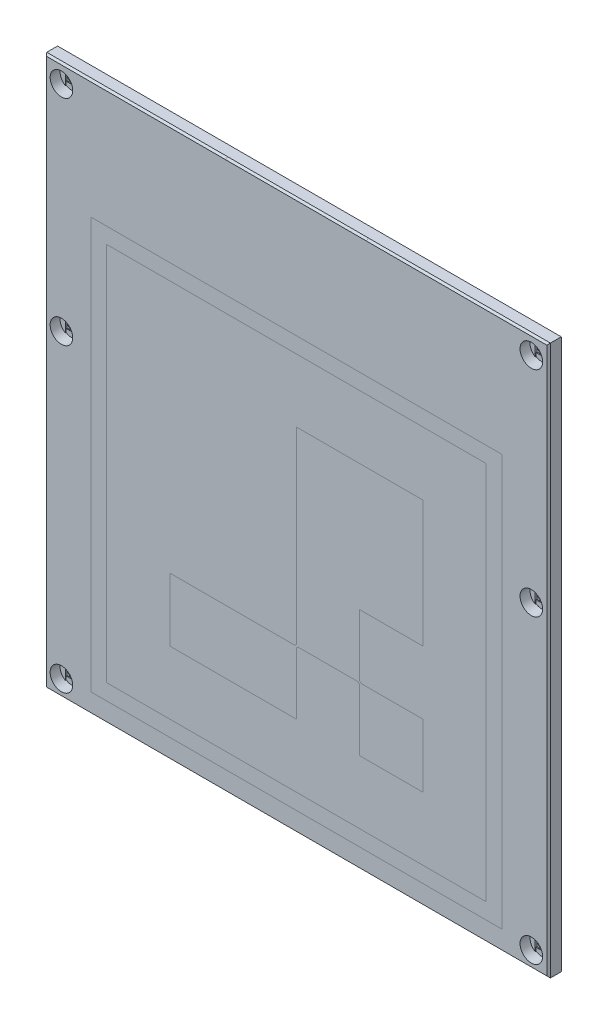
SolidWorks part; units mm, degrees
ref_plane "Front Plane" through (0, 0, 0) normal (0, 0, 1) x (1, 0, 0)
ref_plane "Top Plane" through (0, 0, 0) normal (0, 1, 0) x (1, 0, 0)
ref_plane "Right Plane" through (0, 0, 0) normal (1, 0, 0) x (0, 0, -1)
sketch "Sketch1" plane through (0, 0, 0) normal (0, 0, 1) x (1, 0, 0)
  line L0 (48, -68) -> (-48, -68) construction
  line L1 (56, -32.5) -> (56, -60) construction
  line L2 (56, 46) -> (56, -24.5) construction
  line L3 (-56, -24.5) -> (-56, 46) construction
  line L5 (-15, 54.4) -> (-15, 29) construction
  line L6 (-15, 29) -> (15, 29) construction
  line L7 (15, 29) -> (15, 54) construction
  line L8 (48, 54) -> (15, 54) construction
  line L9 (48, -68) -> (-48, -68) construction
  line L10 (56, -32.5) -> (56, -60) construction
  line L11 (56, 46) -> (56, -24.5) construction
  line L12 (-56, -24.5) -> (-56, 46) construction
  line L13 (-15, 54.4) -> (-48, 54.4) construction
  line L14 (-15, 54.4) -> (-15, 29) construction
  line L15 (-15, 29) -> (15, 29) construction
  line L16 (15, 29) -> (15, 54) construction
  line L17 (48, 54) -> (15, 54) construction
  line L18 (-15.25, 54.05) -> (-15.25, 28.75)
  line L19 (-55.65, 54.05) -> (-15.25, 54.05)
  line L20 (-55.65, 54.05) -> (-55.65, -67.65)
  line L21 (-55.65, -67.65) -> (55.825, -67.65)
  line L22 (55.825, 54.05) -> (55.825, -67.65)
  line L23 (-15.25, 28.75) -> (15.125, 28.75)
  line L24 (15.125, 28.75) -> (15.125, 54.05)
  line L25 (15.125, 54.05) -> (55.825, 54.05)
  circle A0 centre (-52, -64) radius 2.1 construction
  circle A3 centre (52, 50) radius 2.1 construction
  circle A4 centre (-52, 50) radius 2.1 construction
  circle A5 centre (-52, -64) radius 2.1 construction
  circle A6 centre (-52, 2.6) radius 2.15 construction
  circle A7 centre (52, 2.6) radius 2.15 construction
  circle A8 centre (52, 50) radius 2.1 construction
  circle A9 centre (-52, 50) radius 2.1 construction
  circle A10 centre (-52, 50) radius 1.35
  circle A11 centre (-52, 2.6) radius 1.35
  circle A12 centre (-52, -64) radius 1.35
  circle A13 centre (52, 50) radius 1.35
  circle A14 centre (52, 2.6) radius 1.35
  circle A15 centre (52, -64) radius 1.35
  circle A16 centre (-52, 2.6) radius 2.15 construction
  circle A17 centre (52, 2.6) radius 2.15 construction
  dimension "D5" = 2.7
  dimension "D1" = 0.35
  dimension "D2" = 0.35
  dimension "D3" = 0.35
  dimension "D4" = 0.35
  dimension "D6" = 0.25
  dimension "D7" = 0.25
  dimension "D8" = 0.25
extrude "Boss-Extrude1" add sketch "Sketch1" along normal blind 2.8
sketch "Sketch2" plane through (0, 0, 2.8) normal (0, 0, 1) x (1, 0, 0)
  line L5 (15.125, 28.75) -> (-15.25, 28.75) construction
  line L8 (-45.5, -63.25) -> (45.5, -63.25)
  line L9 (-45.5, -63.25) -> (-45.5, 27.75)
  line L10 (-45.5, 27.75) -> (45.5, 27.75)
  line L11 (45.5, -63.25) -> (45.5, 27.75)
  line L31 (-42, 24.25) -> (-28, 24.25)
  line L32 (-42, 24.25) -> (-42, 10.25)
  line L33 (-42, 10.25) -> (-28, 10.25)
  line L34 (-28, 24.25) -> (-28, 10.25)
  line L35 (-28, 24.25) -> (-14, 24.25)
  line L36 (-28, 24.25) -> (-28, 10.25)
  line L37 (-28, 10.25) -> (-14, 10.25)
  line L38 (-14, 24.25) -> (-14, 10.25)
  line L39 (-14, 24.25) -> (0, 24.25)
  line L40 (-14, 24.25) -> (-14, 10.25)
  line L41 (-14, 10.25) -> (0, 10.25)
  line L42 (0, 24.25) -> (0, 10.25)
  line L43 (0, 24.25) -> (14, 24.25)
  line L44 (0, 24.25) -> (0, 10.25)
  line L45 (0, 10.25) -> (14, 10.25)
  line L46 (14, 24.25) -> (14, 10.25)
  line L47 (14, 24.25) -> (28, 24.25)
  line L48 (14, 24.25) -> (14, 10.25)
  line L49 (14, 10.25) -> (28, 10.25)
  line L50 (28, 24.25) -> (28, 10.25)
  line L51 (28, 24.25) -> (42, 24.25)
  line L52 (28, 24.25) -> (28, 10.25)
  line L53 (28, 10.25) -> (42, 10.25)
  line L54 (42, 24.25) -> (42, 10.25)
  line L55 (-42, 10.25) -> (-28, 10.25)
  line L56 (-42, 10.25) -> (-42, -3.75)
  line L57 (-42, -3.75) -> (-28, -3.75)
  line L58 (-28, 10.25) -> (-28, -3.75)
  line L59 (-28, -3.75) -> (-14, -3.75)
  line L60 (-28, -3.75) -> (-28, 10.25)
  line L61 (-28, 10.25) -> (-14, 10.25)
  line L62 (-14, -3.75) -> (-14, 10.25)
  line L63 (-14, -3.75) -> (0, -3.75)
  line L64 (-14, -3.75) -> (-14, 10.25)
  line L65 (-14, 10.25) -> (0, 10.25)
  line L66 (0, -3.75) -> (0, 10.25)
  line L67 (0, -3.75) -> (14, -3.75)
  line L68 (0, -3.75) -> (0, 10.25)
  line L69 (0, 10.25) -> (14, 10.25)
  line L70 (14, -3.75) -> (14, 10.25)
  line L71 (14, -3.75) -> (28, -3.75)
  line L72 (14, -3.75) -> (14, 10.25)
  line L73 (14, 10.25) -> (28, 10.25)
  line L74 (28, -3.75) -> (28, 10.25)
  line L75 (28, -3.75) -> (42, -3.75)
  line L76 (28, -3.75) -> (28, 10.25)
  line L77 (28, 10.25) -> (42, 10.25)
  line L78 (42, -3.75) -> (42, 10.25)
  line L79 (42, -3.75) -> (28, -3.75)
  line L80 (42, -3.75) -> (42, -17.75)
  line L81 (42, -17.75) -> (28, -17.75)
  line L82 (28, -3.75) -> (28, -17.75)
  line L83 (14, -3.75) -> (28, -3.75)
  line L84 (14, -3.75) -> (14, -17.75)
  line L85 (14, -17.75) -> (28, -17.75)
  line L86 (28, -3.75) -> (28, -17.75)
  line L87 (0, -3.75) -> (14, -3.75)
  line L88 (0, -3.75) -> (0, -17.75)
  line L89 (0, -17.75) -> (14, -17.75)
  line L90 (14, -3.75) -> (14, -17.75)
  line L91 (-14, -3.75) -> (0, -3.75)
  line L92 (-14, -3.75) -> (-14, -17.75)
  line L93 (-14, -17.75) -> (0, -17.75)
  line L94 (0, -3.75) -> (0, -17.75)
  line L95 (-28, -3.75) -> (-14, -3.75)
  line L96 (-28, -3.75) -> (-28, -17.75)
  line L97 (-28, -17.75) -> (-14, -17.75)
  line L98 (-14, -3.75) -> (-14, -17.75)
  line L99 (-42, -3.75) -> (-28, -3.75)
  line L100 (-42, -3.75) -> (-42, -17.75)
  line L101 (-42, -17.75) -> (-28, -17.75)
  line L102 (-28, -3.75) -> (-28, -17.75)
  line L103 (-42, -17.75) -> (-28, -17.75)
  line L104 (-42, -17.75) -> (-42, -31.75)
  line L105 (-42, -31.75) -> (-28, -31.75)
  line L106 (-28, -17.75) -> (-28, -31.75)
  line L107 (-28, -31.75) -> (-14, -31.75)
  line L108 (-28, -31.75) -> (-28, -17.75)
  line L109 (-28, -17.75) -> (-14, -17.75)
  line L110 (-14, -31.75) -> (-14, -17.75)
  line L111 (-14, -17.75) -> (0, -17.75)
  line L112 (-14, -17.75) -> (-14, -31.75)
  line L113 (-14, -31.75) -> (0, -31.75)
  line L114 (0, -17.75) -> (0, -31.75)
  line L115 (0, -31.75) -> (14, -31.75)
  line L116 (0, -31.75) -> (0, -17.75)
  line L117 (0, -17.75) -> (14, -17.75)
  line L118 (14, -31.75) -> (14, -17.75)
  line L119 (14, -31.75) -> (28, -31.75)
  line L120 (14, -31.75) -> (14, -17.75)
  line L121 (14, -17.75) -> (28, -17.75)
  line L122 (28, -31.75) -> (28, -17.75)
  line L123 (28, -31.75) -> (42, -31.75)
  line L124 (28, -31.75) -> (28, -17.75)
  line L125 (28, -17.75) -> (42, -17.75)
  line L126 (42, -31.75) -> (42, -17.75)
  line L127 (-42, -31.75) -> (-28, -31.75)
  line L128 (-42, -31.75) -> (-42, -45.75)
  line L129 (-42, -45.75) -> (-28, -45.75)
  line L130 (-28, -31.75) -> (-28, -45.75)
  line L131 (-28, -45.75) -> (-14, -45.75)
  line L132 (-28, -45.75) -> (-28, -31.75)
  line L133 (-28, -31.75) -> (-14, -31.75)
  line L134 (-14, -45.75) -> (-14, -31.75)
  line L135 (-14, -45.75) -> (0, -45.75)
  line L136 (-14, -45.75) -> (-14, -31.75)
  line L137 (-14, -31.75) -> (0, -31.75)
  line L138 (0, -45.75) -> (0, -31.75)
  line L139 (0, -45.75) -> (14, -45.75)
  line L140 (0, -45.75) -> (0, -31.75)
  line L141 (0, -31.75) -> (14, -31.75)
  line L142 (14, -45.75) -> (14, -31.75)
  line L143 (14, -45.75) -> (28, -45.75)
  line L144 (14, -45.75) -> (14, -31.75)
  line L145 (14, -31.75) -> (28, -31.75)
  line L146 (28, -45.75) -> (28, -31.75)
  line L147 (28, -45.75) -> (42, -45.75)
  line L148 (28, -45.75) -> (28, -31.75)
  line L149 (28, -31.75) -> (42, -31.75)
  line L150 (42, -45.75) -> (42, -31.75)
  line L151 (42, -45.75) -> (28, -45.75)
  line L152 (42, -45.75) -> (42, -59.75)
  line L153 (42, -59.75) -> (28, -59.75)
  line L154 (28, -45.75) -> (28, -59.75)
  line L155 (28, -59.75) -> (14, -59.75)
  line L156 (28, -59.75) -> (28, -45.75)
  line L157 (28, -45.75) -> (14, -45.75)
  line L158 (14, -59.75) -> (14, -45.75)
  line L159 (0, -45.75) -> (14, -45.75)
  line L160 (0, -45.75) -> (0, -59.75)
  line L161 (0, -59.75) -> (14, -59.75)
  line L162 (14, -45.75) -> (14, -59.75)
  line L163 (-14, -45.75) -> (0, -45.75)
  line L164 (-14, -45.75) -> (-14, -59.75)
  line L165 (-14, -59.75) -> (0, -59.75)
  line L166 (0, -45.75) -> (0, -59.75)
  line L167 (-28, -45.75) -> (-14, -45.75)
  line L168 (-28, -45.75) -> (-28, -59.75)
  line L169 (-28, -59.75) -> (-14, -59.75)
  line L170 (-14, -45.75) -> (-14, -59.75)
  line L171 (-42, -45.75) -> (-28, -45.75)
  line L172 (-42, -45.75) -> (-42, -59.75)
  line L173 (-42, -59.75) -> (-28, -59.75)
  line L174 (-28, -45.75) -> (-28, -59.75)
  point P3 (0, 27.75)
  point P58 (-45.5, -17.75)
  dimension "D1" = 1
  dimension "D2" = 91
  dimension "D3" = 14
sketch "Sketch3" plane through (0, 0, 2.8) normal (0, 0, 1) x (1, 0, 0)
  circle A0 centre (-52, 50) radius 2.5
  circle A1 centre (-52, 2.6) radius 2.5
  circle A2 centre (-52, -64) radius 2.5
  circle A3 centre (52, -64) radius 2.5
  circle A4 centre (52, 2.6) radius 2.5
  circle A5 centre (52, 50) radius 2.5
  dimension "D1" = 5
extrude "Cut-Extrude1" cut sketch "Sketch3" against normal blind 2.2
sketch "Sketch4" plane through (0, 0, 0) normal (0, 0, -1) x (-1, 0, 0)
  line L0 (-15.125, 28.75) -> (15.25, 28.75) construction
  line L1 (-45.65, -57.65) -> (45.65, -57.65)
  line L2 (-45.65, -57.65) -> (-45.65, 27.75)
  line L3 (-45.65, 27.75) -> (45.65, 27.75)
  line L4 (45.65, -57.65) -> (45.65, 27.75)
  line L5 (-45.65, -57.65) -> (45.65, 27.75) construction
  line L6 (-45.65, 27.75) -> (45.65, -57.65) construction
  line L7 (55.65, 54.05) -> (55.65, -67.65) construction
  line L8 (55.65, -67.65) -> (-55.825, -67.65) construction
  point P0 (0, -14.95)
  point P9 (0, 27.75)
  dimension "D1" = 1
  dimension "D2" = 10
  dimension "D3" = 10
extrude "Cut-Extrude2" cut sketch "Sketch4" against normal blind 1.5
sketch "Sketch5" plane through (0, 0, 0.6) normal (0, 0, 1) x (1, 0, 0)
  line L2 (-53.35, 47.8958) -> (-53.35, 52.1042)
  line L4 (-50.65, 47.8958) -> (-50.65, 52.1042)
  line L5 (-53.35, 47.8958) -> (-50.65, 52.1042) construction
  line L6 (-53.35, 52.1042) -> (-50.65, 47.8958) construction
  line L8 (-53.35, 0.4958) -> (-53.35, 4.7042)
  line L10 (-50.65, 0.4958) -> (-50.65, 4.7042)
  line L11 (-53.35, 0.4958) -> (-50.65, 4.7042) construction
  line L12 (-53.35, 4.7042) -> (-50.65, 0.4958) construction
  line L14 (-53.35, -66.1042) -> (-53.35, -61.8958)
  line L16 (-50.65, -66.1042) -> (-50.65, -61.8958)
  line L17 (-53.35, -66.1042) -> (-50.65, -61.8958) construction
  line L18 (-53.35, -61.8958) -> (-50.65, -66.1042) construction
  circle A0 centre (-52, 50) radius 2.5 construction
  circle A1 centre (-52, 50) radius 1.35 construction
  arc A2 (-50.65, 52.1042) -> (-53.35, 52.1042) centre (-52, 50) ccw
  arc A3 (-53.35, 47.8958) -> (-50.65, 47.8958) centre (-52, 50) ccw
  circle A4 centre (-52, 2.6) radius 2.5 construction
  circle A5 centre (-52, 2.6) radius 1.35 construction
  circle A6 centre (-52, 2.6) radius 2.5 construction
  arc A7 (-50.65, 4.7042) -> (-53.35, 4.7042) centre (-52, 2.6) ccw
  arc A8 (-53.35, 0.4958) -> (-50.65, 0.4958) centre (-52, 2.6) ccw
  circle A9 centre (-52, -64) radius 2.5 construction
  circle A10 centre (-52, -64) radius 1.35 construction
  circle A11 centre (-52, -64) radius 2.5 construction
  arc A12 (-50.65, -61.8958) -> (-53.35, -61.8958) centre (-52, -64) ccw
  arc A13 (-53.35, -66.1042) -> (-50.65, -66.1042) centre (-52, -64) ccw
  point P0 (-52, 50)
  point P10 (-52, 2.6)
  point P22 (-52, -64)
extrude "Cut-Extrude3" cut sketch "Sketch5" against normal blind 0.2
sketch "Sketch6" plane through (0, 0, 0.4) normal (0, 0, 1) x (1, 0, 0)
  line L0 (-50.65, -66.1042) -> (-50.65, -61.8958) construction
  line L1 (-53.35, -65.35) -> (-50.65, -65.35)
  line L2 (-53.35, -65.35) -> (-53.35, -62.65)
  line L3 (-53.35, -62.65) -> (-50.65, -62.65)
  line L4 (-50.65, -65.35) -> (-50.65, -62.65)
  line L5 (-53.35, -65.35) -> (-50.65, -62.65) construction
  line L6 (-53.35, -62.65) -> (-50.65, -65.35) construction
  line L7 (-50.65, 0.4958) -> (-50.65, 4.7042) construction
  line L8 (-53.35, 1.25) -> (-50.65, 1.25)
  line L9 (-53.35, 1.25) -> (-53.35, 3.95)
  line L10 (-53.35, 3.95) -> (-50.65, 3.95)
  line L11 (-50.65, 1.25) -> (-50.65, 3.95)
  line L12 (-53.35, 1.25) -> (-50.65, 3.95) construction
  line L13 (-53.35, 3.95) -> (-50.65, 1.25) construction
  line L14 (-50.65, 47.8958) -> (-50.65, 52.1042) construction
  line L15 (-53.35, 48.65) -> (-50.65, 48.65)
  line L16 (-53.35, 48.65) -> (-53.35, 51.35)
  line L17 (-53.35, 51.35) -> (-50.65, 51.35)
  line L18 (-50.65, 48.65) -> (-50.65, 51.35)
  line L19 (-53.35, 48.65) -> (-50.65, 51.35) construction
  line L20 (-53.35, 51.35) -> (-50.65, 48.65) construction
  arc A0 (-50.65, -64) -> (-53.35, -64) centre (-52, -64) ccw construction
  arc A1 (-50.65, 2.6) -> (-53.35, 2.6) centre (-52, 2.6) ccw construction
  arc A2 (-50.65, 50) -> (-53.35, 50) centre (-52, 50) ccw construction
  point P0 (-52, -64)
  point P11 (-52, 2.6)
  point P22 (-52, 50)
extrude "Cut-Extrude4" cut sketch "Sketch6" against normal blind 0.2
mirror "Mirror1" about plane through (0, 0, 0) normal (1, 0, 0) of "Cut-Extrude4", "Cut-Extrude3"
chamfer "Chamfer1" distance 0.4 angle 45 8 edges at (0.0875, -67.65, 2.8) (55.825, -6.8, 2.8) (35.475, 54.05, 2.8) (15.125, 41.4, 2.8) (-0.0625, 28.75, 2.8) (-15.25, 41.4, 2.8) (-35.45, 54.05, 2.8) (-55.65, -6.8, 2.8)
sketch "Sketch7" plane through (0, 0, 2.8) normal (0, 0, 1) x (1, 0, 0)
  line L0 (28, 24.25) -> (42, 24.25) construction
  line L1 (14, 24.25) -> (28, 24.25) construction
  line L2 (0, 24.25) -> (14, 24.25) construction
  line L3 (-14, 24.25) -> (0, 24.25) construction
  line L4 (-28, 24.25) -> (-14, 24.25) construction
  line L5 (-42, 24.25) -> (-28, 24.25) construction
  line L6 (-42, 24.25) -> (-42, 10.25) construction
  line L7 (-42, 10.25) -> (-42, -3.75) construction
  line L8 (-42, -3.75) -> (-42, -17.75) construction
  line L9 (-42, -17.75) -> (-42, -31.75) construction
  line L10 (-42, -31.75) -> (-42, -45.75) construction
  line L11 (-42, -45.75) -> (-42, -59.75) construction
  line L12 (-42, -59.75) -> (-28, -59.75) construction
  line L13 (-28, -59.75) -> (-14, -59.75) construction
  line L14 (-14, -59.75) -> (0, -59.75) construction
  line L15 (0, -59.75) -> (14, -59.75) construction
  line L16 (28, -59.75) -> (14, -59.75) construction
  line L17 (42, -59.75) -> (28, -59.75) construction
  line L18 (42, -45.75) -> (42, -59.75) construction
  line L19 (42, -45.75) -> (42, -31.75) construction
  line L20 (42, -31.75) -> (42, -17.75) construction
  line L21 (42, -3.75) -> (42, -17.75) construction
  line L22 (42, -3.75) -> (42, 10.25) construction
  line L23 (42, 24.25) -> (42, 10.25) construction
  line L24 (45.5, -63.25) -> (45.5, 27.75) construction
  line L25 (-45.5, -63.25) -> (45.5, -63.25) construction
  line L26 (-45.5, -63.25) -> (-45.5, 27.75) construction
  line L27 (-45.5, 27.75) -> (45.5, 27.75) construction
  line L28 (28, 24.25) -> (42, 24.25)
  line L29 (14, 24.25) -> (28, 24.25)
  line L30 (0, 24.25) -> (14, 24.25)
  line L31 (-14, 24.25) -> (0, 24.25)
  line L32 (-28, 24.25) -> (-14, 24.25)
  line L33 (-42, 24.25) -> (-28, 24.25)
  line L34 (-42, 24.25) -> (-42, 10.25)
  line L35 (-42, 10.25) -> (-42, -3.75)
  line L36 (-42, -3.75) -> (-42, -17.75)
  line L37 (-42, -17.75) -> (-42, -31.75)
  line L38 (-42, -31.75) -> (-42, -45.75)
  line L39 (-42, -45.75) -> (-42, -59.75)
  line L40 (-42, -59.75) -> (-28, -59.75)
  line L41 (-28, -59.75) -> (-14, -59.75)
  line L42 (-14, -59.75) -> (0, -59.75)
  line L43 (0, -59.75) -> (14, -59.75)
  line L44 (28, -59.75) -> (14, -59.75)
  line L45 (42, -59.75) -> (28, -59.75)
  line L46 (42, -45.75) -> (42, -59.75)
  line L47 (42, -45.75) -> (42, -31.75)
  line L48 (42, -31.75) -> (42, -17.75)
  line L49 (42, -3.75) -> (42, -17.75)
  line L50 (42, -3.75) -> (42, 10.25)
  line L51 (42, 24.25) -> (42, 10.25)
  line L52 (45.5, -63.25) -> (45.5, 27.75)
  line L53 (-45.5, -63.25) -> (45.5, -63.25)
  line L54 (-45.5, -63.25) -> (-45.5, 27.75)
  line L55 (-45.5, 27.75) -> (45.5, 27.75)
extrude "Cut-Extrude5" cut sketch "Sketch7" against normal blind 0.4
sketch "Sketch8" plane through (0, 0, 2.4) normal (0, 0, 1) x (1, 0, 0)
  line L0 (-42, -59.75) -> (42, -59.75) construction
  line L1 (42, -59.75) -> (42, 24.25) construction
  line L2 (42, 24.25) -> (-42, 24.25) construction
  line L3 (-42, 24.25) -> (-42, -59.75) construction
  line L4 (-45.5, -63.25) -> (45.5, -63.25)
  line L5 (45.5, -63.25) -> (45.5, 27.75)
  line L6 (45.5, 27.75) -> (-45.5, 27.75)
  line L7 (-45.5, 27.75) -> (-45.5, -63.25)
  line L8 (-45.5, -63.25) -> (45.5, -63.25)
  line L9 (45.5, -63.25) -> (45.5, 27.75)
  line L10 (45.5, 27.75) -> (-45.5, 27.75)
  line L11 (-45.5, 27.75) -> (-45.5, -63.25)
  line L12 (-42, -59.75) -> (42, -59.75)
  line L13 (42, -59.75) -> (42, 24.25)
  line L14 (42, 24.25) -> (-42, 24.25)
  line L15 (-42, 24.25) -> (-42, -59.75)
  dimension "D1" = 0
extrude "Boss-Extrude2" add sketch "Sketch8" along normal up to surface (0.4 mm away) separate body up to face at (0, -17.75, 2.8)
sketch "Sketch9" plane through (0, 0, 2.8) normal (0, 0, 1) x (1, 0, 0)
  line L40 (-28, -31.75) -> (-28, -45.75) construction
  line L41 (-28, -31.75) -> (-14, -31.75) construction
  line L42 (-14, -31.75) -> (0, -31.75) construction
  line L43 (0, -17.75) -> (0, -31.75) construction
  line L44 (0, -3.75) -> (0, -17.75) construction
  line L45 (0, -3.75) -> (0, 10.25) construction
  line L46 (0, 10.25) -> (14, 10.25) construction
  line L47 (14, 10.25) -> (28, 10.25) construction
  line L48 (28, -3.75) -> (28, 10.25) construction
  line L49 (28, -3.75) -> (28, -17.75) construction
  line L50 (14, -17.75) -> (28, -17.75) construction
  line L51 (14, -31.75) -> (14, -17.75) construction
  line L52 (14, -31.75) -> (28, -31.75) construction
  line L53 (28, -45.75) -> (28, -31.75) construction
  line L54 (14, -45.75) -> (28, -45.75) construction
  line L55 (14, -45.75) -> (14, -31.75) construction
  line L56 (0, -31.75) -> (14, -31.75) construction
  line L57 (0, -45.75) -> (0, -31.75) construction
  line L58 (-14, -45.75) -> (0, -45.75) construction
  line L59 (-28, -45.75) -> (-14, -45.75) construction
  line L60 (-28, -31.75) -> (-28, -45.75)
  line L61 (-28, -31.75) -> (-14, -31.75)
  line L62 (-14, -31.75) -> (-0.3536, -31.75)
  line L63 (0, -17.75) -> (0, -31.3964)
  line L64 (0, -3.75) -> (0, -17.75)
  line L65 (0, -3.75) -> (0, 10.25)
  line L66 (0, 10.25) -> (14, 10.25)
  line L67 (14, 10.25) -> (28, 10.25)
  line L68 (28, -3.75) -> (28, 10.25)
  line L69 (28, -3.75) -> (28, -17.75)
  line L70 (14, -17.75) -> (28, -17.75)
  line L71 (14, -31.3964) -> (14, -17.75)
  line L72 (14.3536, -31.75) -> (28, -31.75)
  line L73 (28, -45.75) -> (28, -31.75)
  line L74 (14, -45.75) -> (28, -45.75)
  line L75 (14, -45.75) -> (14, -32.1036)
  line L76 (0.3536, -31.75) -> (13.6464, -31.75)
  line L77 (0, -45.75) -> (0, -32.1036)
  line L78 (-14, -45.75) -> (0, -45.75)
  line L79 (-28, -45.75) -> (-14, -45.75)
  line L80 (0, -31.3964) -> (-0.3536, -31.75)
  line L81 (0, -32.1036) -> (0.3536, -31.75)
  line L82 (13.6464, -31.75) -> (14, -32.1036)
  line L83 (14.3536, -31.75) -> (14, -31.3964)
  dimension "D1" = 45
  dimension "D2" = 0.5
  dimension "D3" = 45
  dimension "D4" = 0.5
extrude "Cut-Extrude6" cut sketch "Sketch9" against normal blind 0.4 contours L63 L76 L71 L70 L69 L68 L67 L66 L65 L64 region at (7, -19.502, 2.8)
sketch "Sketch10" plane through (0, 0, 2.4) normal (0, 0, 1) x (1, 0, 0)
  line L42 (28, -31.75) -> (14.3536, -31.75)
  line L43 (14.3536, -31.75) -> (14, -31.3964)
  line L44 (14, -31.3964) -> (14, -17.75)
  line L45 (14, -17.75) -> (28, -17.75)
  line L46 (28, -17.75) -> (28, 10.25)
  line L47 (28, 10.25) -> (0, 10.25)
  line L48 (0, 10.25) -> (0, -31.3964)
  line L49 (0, -31.3964) -> (-0.3536, -31.75)
  line L50 (-0.3536, -31.75) -> (-28, -31.75)
  line L51 (-28, -31.75) -> (-28, -45.75)
  line L52 (-28, -45.75) -> (0, -45.75)
  line L53 (0, -45.75) -> (0, -32.1036)
  line L54 (0, -32.1036) -> (0.3536, -31.75)
  line L55 (0.3536, -31.75) -> (13.6464, -31.75)
  line L56 (13.6464, -31.75) -> (14, -32.1036)
  line L57 (14, -32.1036) -> (14, -45.75)
  line L58 (14, -45.75) -> (28, -45.75)
  line L59 (28, -45.75) -> (28, -31.75)
  line L60 (28, -31.75) -> (14.3536, -31.75)
  line L61 (14.3536, -31.75) -> (14, -31.3964)
  line L62 (14, -31.3964) -> (14, -17.75)
  line L63 (14, -17.75) -> (28, -17.75)
  line L64 (28, -17.75) -> (28, 10.25)
  line L65 (28, 10.25) -> (0, 10.25)
  line L66 (0, 10.25) -> (0, -31.3964)
  line L67 (0, -31.3964) -> (-0.3536, -31.75)
  line L68 (-0.3536, -31.75) -> (-28, -31.75)
  line L69 (-28, -31.75) -> (-28, -45.75)
  line L70 (-28, -45.75) -> (0, -45.75)
  line L71 (0, -45.75) -> (0, -32.1036)
  line L72 (0, -32.1036) -> (0.3536, -31.75)
  line L73 (0.3536, -31.75) -> (13.6464, -31.75)
  line L74 (13.6464, -31.75) -> (14, -32.1036)
  line L75 (14, -32.1036) -> (14, -45.75)
  line L76 (14, -45.75) -> (28, -45.75)
  line L77 (28, -45.75) -> (28, -31.75)
  line M69 (28, -31.75) -> (14.3536, -31.75)
  line M70 (14.3536, -31.75) -> (14, -31.3964)
  line M71 (14, -31.3964) -> (14, -17.75)
  line M72 (14, -17.75) -> (28, -17.75)
  line M73 (28, -17.75) -> (28, 10.25)
  line M74 (28, 10.25) -> (0, 10.25)
  line M75 (0, 10.25) -> (0, -31.3964)
  line M76 (0, -31.3964) -> (-0.3536, -31.75)
  line M77 (-0.3536, -31.75) -> (-28, -31.75)
  line M78 (-28, -31.75) -> (-28, -45.75)
  line M79 (-28, -45.75) -> (0, -45.75)
  line M80 (0, -45.75) -> (0, -32.1036)
  line M81 (0, -32.1036) -> (0.3536, -31.75)
  line M82 (0.3536, -31.75) -> (13.6464, -31.75)
  line M83 (13.6464, -31.75) -> (14, -32.1036)
  line M84 (14, -32.1036) -> (14, -45.75)
  line M85 (14, -45.75) -> (28, -45.75)
  line M86 (28, -45.75) -> (28, -31.75)
  dimension "D1" = 0
extrude "Boss-Extrude3" add sketch "Sketch10" along normal up to surface (0.4 mm away) separate body contours M86 M69 M70 M71 M72 M73 M74 M75 M76 M77 M78 M79 M80 M81 M82 M83 M84 M85 region at (7, -19.502, 2.4) up to face at (0, -17.75, 2.8)
sketch "Sketch11" plane through (0, 0, 2.8) normal (0, 0, 1) x (1, 0, 0)
  line L0 (15.125, 54.05) -> (55.825, 54.05) construction
  line L1 (-15.65, 28.35) -> (15.525, 28.35)
  line L2 (-15.65, 28.35) -> (-15.65, 54.05)
  line L3 (-15.65, 54.05) -> (15.525, 54.05)
  line L4 (15.525, 28.35) -> (15.525, 54.05)
  line L5 (15.525, 53.65) -> (15.525, 28.35) construction
extrude "Boss-Extrude4" add sketch "Sketch11" against normal up to surface (2.8 mm away) up to face at (0, -14.95, 0)
chamfer "Chamfer2" distance 0.4 angle 45 1 edges at (-0.0625, 54.05, 2.8)
